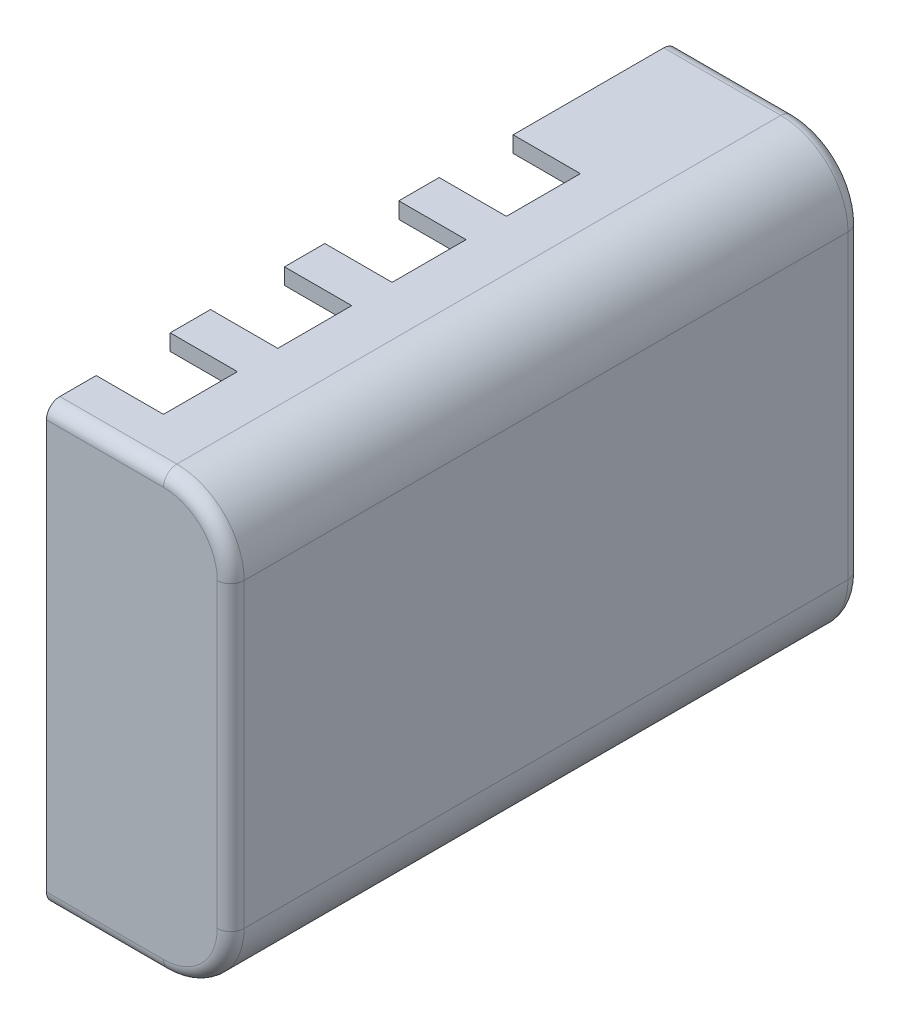
SolidWorks part; units mm, degrees
ref_plane "Front Plane" through (0, 0, 0) normal (0, 0, 1) x (1, 0, 0)
ref_plane "Top Plane" through (0, 0, 0) normal (0, 1, 0) x (1, 0, 0)
ref_plane "Right Plane" through (0, 0, 0) normal (1, 0, 0) x (0, 0, -1)
sketch "Sketch1" plane through (0, 0, 0) normal (1, 0, 0) x (0, 0, -1)
  line L1 (-22.25, -15) -> (22.25, -15)
  line L2 (-22.25, -15) -> (-22.25, 15)
  line L3 (-22.25, 15) -> (22.25, 15)
  line L4 (22.25, -15) -> (22.25, 15)
  line L5 (-22.25, -15) -> (22.25, 15) construction
  line L6 (-22.25, 15) -> (22.25, -15) construction
  point P0 (0, 0)
  dimension "D1" = 44.5
  dimension "D2" = 30
extrude "Boss-Extrude1" add sketch "Sketch1" along normal blind 12.5
shell "Shell2" thickness 1.2 removed face at (0, 0, 0) outward yes
sketch "Sketch2" plane through (0, 15, 0) normal (0, -1, 0) x (1, 0, 0)
  line L0 (0, 19.75) -> (0, 14.25)
  line L1 (0, 19.75) -> (5, 19.75)
  line L2 (0, 14.25) -> (5, 14.25)
  line L3 (5, 19.75) -> (5, 14.25)
  line L4 (0, -22.25) -> (0, 22.25) construction
  line L5 (0, 11.25) -> (0, 5.75)
  line L6 (0, 11.25) -> (5, 11.25)
  line L7 (0, 5.75) -> (5, 5.75)
  line L8 (5, 11.25) -> (5, 5.75)
  line L10 (0, -23.45) -> (0, 23.45) construction
  line L11 (0, 2.75) -> (5, 2.75)
  line L12 (0, 2.75) -> (0, -2.75)
  line L13 (5, 2.75) -> (5, -2.75)
  line L14 (0, -2.75) -> (5, -2.75)
  line L15 (0, -5.75) -> (5, -5.75)
  line L16 (0, -5.75) -> (0, -11.25)
  line L17 (5, -5.75) -> (5, -11.25)
  line L18 (0, -11.25) -> (5, -11.25)
  dimension "D1" = 2.5
  dimension "D2" = 5.5
  dimension "D3" = 5
  dimension "D4" = 3
  dimension "D5" = 5.5
  dimension "D6" = 3
  dimension "D7" = 5.5
  dimension "D8" = 5.5
  dimension "D9" = 3
extrude "Cut-Extrude1" cut sketch "Sketch2" against normal up to surface (1.2 mm away) up to face at (6.85, 16.2, 0)
sketch "Sketch3" plane through (0, 0, -23.45) normal (0, 0, -1) x (-1, 0, 0)
  line L0 (0, -16.2) -> (0, 16.2) construction
  line L1 (0, 3) -> (-1.95, 3)
  line L2 (0, 3) -> (0, -1.5)
  line L3 (0, -1.5) -> (-1.95, -1.5)
  line L4 (-12.5, 15) -> (0, 15) construction
  line L5 (-12.5, 15) -> (0, 15) construction
  line L7 (0, 12) -> (-4.2, 12)
  line L8 (0, 12) -> (0, 7)
  line L9 (0, 7) -> (-4.2, 7)
  line L10 (-4.2, 12) -> (-4.2, 7)
  arc A0 (-1.95, -1.5) -> (-1.95, 3) centre (-1.95, 0.75) cw
  point P7 (-4.2, 0.75)
  dimension "D1" = 4.2
  dimension "D2" = 4.5
  dimension "D3" = 12
  dimension "D4" = 4.2
  dimension "D5" = 5
  dimension "D6" = 3
extrude "Cut-Extrude2" cut sketch "Sketch3" against normal up to surface (1.2 mm away) up to face at (6.25, 0, -22.25)
fillet "Fillet1" radius 5 4 edges at (13.7, 16.2, 0) (12.5, -15, 0) (13.7, -16.2, 0) (12.5, 15, 0)
fillet "Fillet3" radius 1 10 edges at (4.35, -16.2, -23.45) (12.2355, -14.7355, -23.45) (13.7, 0, -23.45) (12.2355, 14.7355, -23.45) (4.35, 16.2, -23.45) (4.35, -16.2, 23.45) (12.2355, -14.7355, 23.45) (13.7, 0, 23.45) (12.2355, 14.7355, 23.45) (4.35, 16.2, 23.45)
